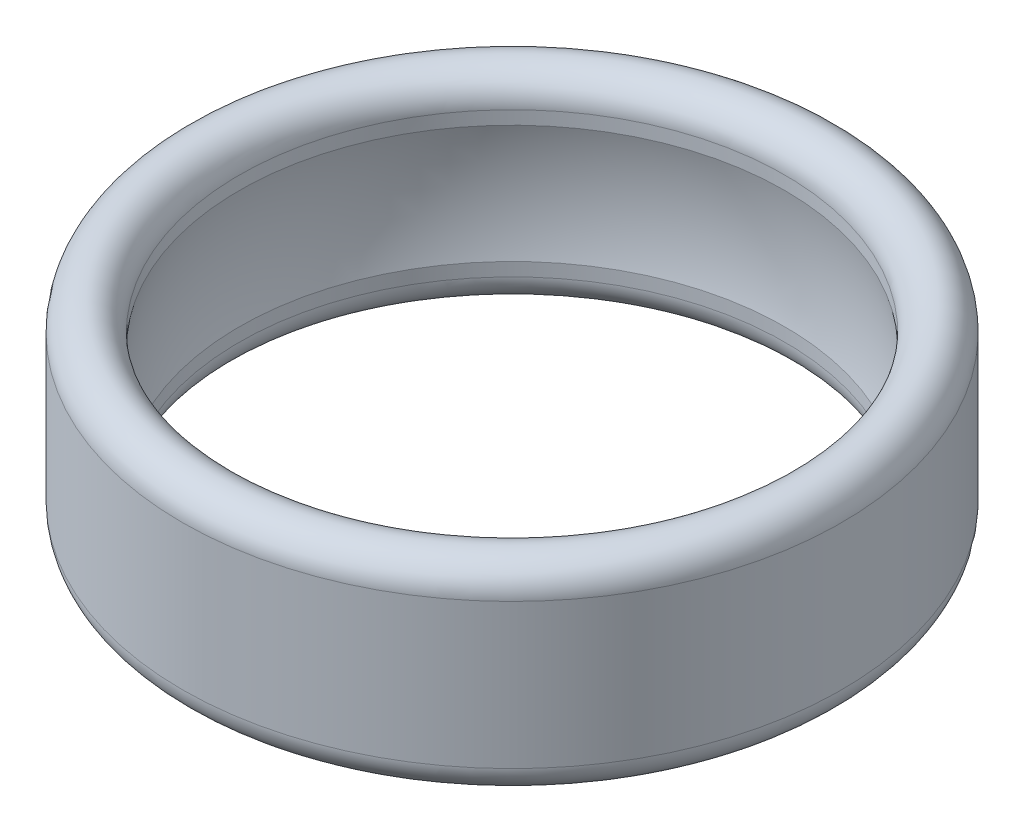
SolidWorks part; units mm, degrees
material "Plain Carbon Steel"
ref_plane "Front Plane" through (0, 0, 0) normal (0, 0, 1) x (1, 0, 0)
ref_plane "Top Plane" through (0, 0, 0) normal (0, 1, 0) x (1, 0, 0)
ref_plane "Right Plane" through (0, 0, 0) normal (1, 0, 0) x (0, 0, -1)
sketch "Sketch2" plane through (0, 0, 0) normal (0, 1, 0) x (1, 0, 0)
  circle A0 centre (0, 0) radius 6.477
  dimension "D1" = 12.954
extrude "Boss-Extrude1" add sketch "Sketch2" along normal blind 3.9624
sketch "Sketch3" plane through (0, 3.9624, 0) normal (0, 1, 0) x (1, 0, 0)
  circle A0 centre (0, 0) radius 5.3594
  dimension "D1" = 10.7188
extrude "Cut-Extrude1" cut sketch "Sketch3" against normal blind 3.9624
sketch "Sketch5" plane through (0, 0, 0) normal (0, 0, 1) x (1, 0, 0)
  line L0 (-5.1068, 3.9624) -> (-5.1068, 0)
  line L1 (-6.477, 0) -> (6.477, 0) construction
  line L2 (6.477, 3.9624) -> (-6.477, 3.9624) construction
  line L3 (0, 0) -> (0, -2.122) construction
  line L4 (5.3594, 3.9624) -> (-5.3594, 3.9624) construction
  arc A1 (-5.1068, 3.9624) -> (-5.1068, 0) centre (-0.127, 1.9812) ccw
  dimension "D2" = 0.127
  dimension "D1" = 5.3594
fillet "Fillet1" 2 edges at (0, 3.9624, 5.3594) (0, 3.9624, 6.477) type full round first side face at (0, 0, 5.3594) second side face at (0, 3.9624, 6.477) middle face at (0, 3.9624, 5.3594)
fillet "Fillet2" 2 edges at (0, 0, 6.477) (0, 0, 5.3594) type full round first side face at (0, 3.4036, 6.477) second side face at (0, 3.4036, 5.3594) middle face at (0, 0, 5.3594)
revolve "Cut-Revolve3" cut sketch "Sketch5" angle 360 about L3
